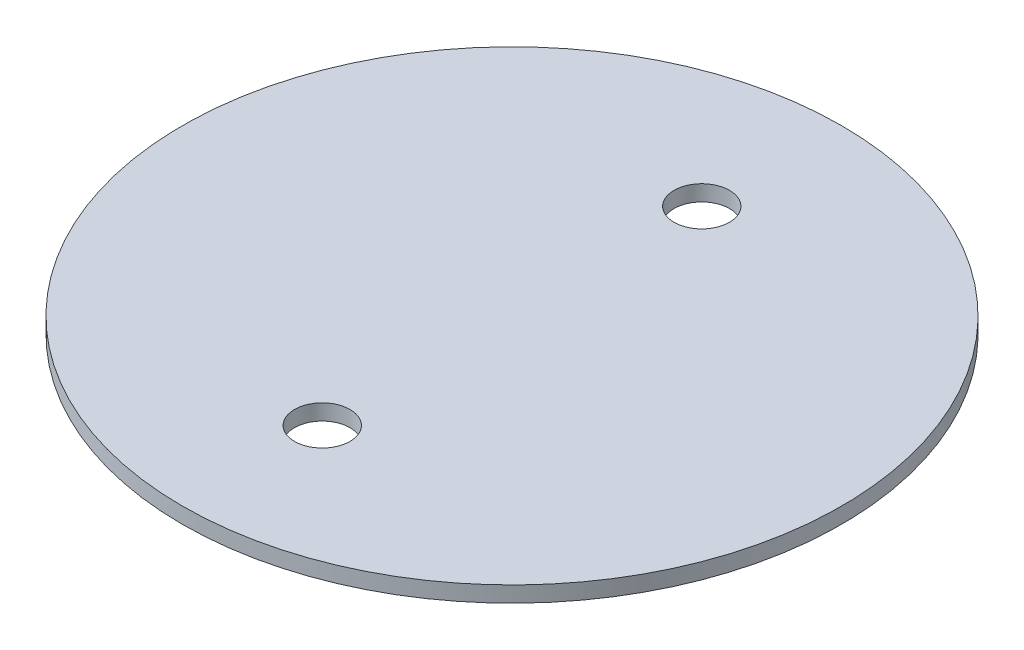
SolidWorks part; units mm, degrees
material "LE Phenolic"
ref_plane "Front Plane" through (0, 0, 0) normal (0, 0, 1) x (1, 0, 0)
ref_plane "Top Plane" through (0, 0, 0) normal (0, 1, 0) x (1, 0, 0)
ref_plane "Right Plane" through (0, 0, 0) normal (1, 0, 0) x (0, 0, -1)
sketch "Sketch1" plane through (0, 0, 0) normal (0, 1, 0) x (1, 0, 0)
  circle A0 centre (0, 0) radius 66.167
  dimension "D1" = 132.334
extrude "Boss-Extrude1" add sketch "Sketch1" along normal blind 3.175
sketch "Sketch2" plane through (0, 0, 0) normal (0, -1, 0) x (1, 0, 0)
  circle A0 centre (0, -38.1) radius 5.5626 construction
  circle A2 centre (0, 38.1) radius 5.5626 construction
  circle A3 centre (0, -38.1) radius 5.5626
  circle A5 centre (0, 38.1) radius 5.5626
extrude "Cut-Extrude1" cut sketch "Sketch2" against normal through all
